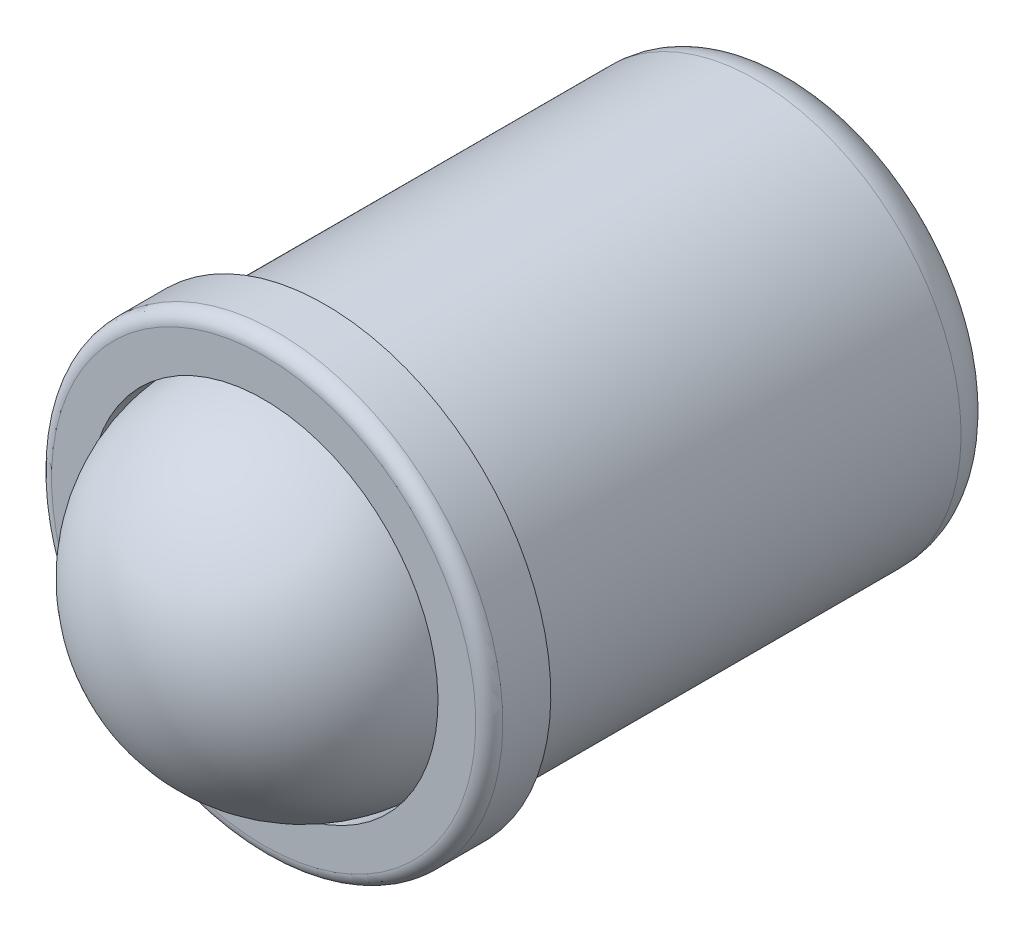
SolidWorks part; units mm, degrees
ref_plane "Front Plane" through (0, 0, 0) normal (0, 0, 1) x (1, 0, 0)
ref_plane "Top Plane" through (0, 0, 0) normal (0, 1, 0) x (1, 0, 0)
ref_plane "Right Plane" through (0, 0, 0) normal (1, 0, 0) x (0, 0, -1)
sketch "Sketch1" plane through (0, 0, 0) normal (1, 0, 0) x (0, 0, -1)
  line L0 (-8.15, 0) -> (8.15, 0) construction
  line L2 (8.15, 2.5) -> (8.15, 5)
  line L3 (8.15, 5) -> (-3.35, 5)
  line L4 (-3.35, 5) -> (-3.35, 5.5)
  line L5 (-3.35, 5.5) -> (-4.85, 5.5)
  line L6 (-4.85, 5.5) -> (-4.85, 4.25)
  line L8 (7.4, 4.25) -> (7.4, 2.5)
  line L9 (7.4, 2.5) -> (8.15, 2.5)
  line L10 (-4.85, 4.25) -> (7.4, 4.25)
  line L11 (-3.9, 0) -> (-3.9, 4.25) construction
  line L12 (-3.9, 4.25) -> (6.9625, 4.25) construction
  line L13 (6.9625, 4.25) -> (6.9625, 3.375) construction
  line L14 (6.9625, 3.375) -> (6.9625, 2.5) construction
  line L15 (6.9625, 2.5) -> (7.4, 2.5) construction
  circle A0 centre (-3.9, 0) radius 4.25
  arc A1 (7.4, 3.75) -> (6.9, 4.25) centre (6.9, 3.75) ccw
  arc A2 (8.15, 4) -> (7.15, 5) centre (7.15, 4) ccw
  arc A3 (-4.52, 5.5) -> (-4.85, 5.17) centre (-4.52, 5.17) ccw
  circle A4 centre (6.9625, 3.375) radius 0.4375
  point P27 (6.9625, 3.8125)
  dimension "R1" = 0.33
  dimension "R2" = 0.5
  dimension "R3" = 1
  dimension "Flange Thickness" = 1.5
  dimension "Body Diameter" = 10
  dimension "Extended Nose Length" = 3.3
  dimension "Rear Inner Diameter" = 5
  dimension "Wall Thickness" = 0.75
  dimension "Flange Diameter" = 11
  dimension "Body Length" = 11.5
  dimension "Nose Diameter" = 8.5
sketch "Sketch2" plane through (0, 0, 0) normal (1, 0, 0) x (0, 0, -1)
  line L0 (7.4, 2.5) -> (8.15, 2.5) construction
  line L2 (8.15, 2.5) -> (8.15, 5) construction
  line L3 (8.15, 5) -> (-3.35, 5) construction
  line L4 (-3.35, 5) -> (-3.35, 5.5) construction
  line L5 (7.4, 4.25) -> (7.4, 2.5) construction
  line L6 (7.4, 3.75) -> (7.4, 2.5)
  line L8 (-4.85, 5.5) -> (-4.85, 4.25) construction
  line L9 (-3.35, 5.5) -> (-4.85, 5.5) construction
  line L10 (7.4, 2.5) -> (8.15, 2.5)
  line L12 (8.15, 2.5) -> (8.15, 4)
  line L13 (7.15, 5) -> (-3.35, 5)
  line L14 (-3.35, 5) -> (-3.35, 5.5)
  line L18 (-4.85, 5.17) -> (-4.85, 4.25)
  line L19 (-3.35, 5.5) -> (-4.52, 5.5)
  line L20 (-4.85, 4.25) -> (7.4, 4.25) construction
  line L21 (-4.85, 4.25) -> (6.9, 4.25)
  arc A0 (7.4, 3.75) -> (6.9, 4.25) centre (6.9, 3.75) ccw construction
  arc A1 (8.15, 4) -> (7.15, 5) centre (7.15, 4) ccw construction
  arc A2 (-4.52, 5.5) -> (-4.85, 5.17) centre (-4.52, 5.17) ccw construction
  arc A3 (7.4, 3.75) -> (6.9, 4.25) centre (6.9, 3.75) ccw
  arc A4 (8.15, 4) -> (7.15, 5) centre (7.15, 4) ccw
  arc A5 (-4.52, 5.5) -> (-4.85, 5.17) centre (-4.52, 5.17) ccw
revolve "Revolve1" add sketch "Sketch2" angle 360 about L0
sketch "Sketch3" plane through (0, 0, 0) normal (1, 0, 0) x (0, 0, -1)
  line L0 (-8.15, 0) -> (8.15, 0) construction
  line L1 (-8.15, 0) -> (0.35, 0)
  circle A0 centre (-3.9, 0) radius 4.25 construction
  arc A1 (0.35, 0) -> (-8.15, 0) centre (-3.9, 0) ccw
revolve "Revolve2" add sketch "Sketch3" angle 360 about L1
ref_plane "Plane1" through (0, 0, -6.9625) normal (0, 0, 1) x (1, 0, 0)
sketch "Sketch4" plane through (0, 0, -6.9625) normal (0, 0, 1) x (1, 0, 0)
  circle A0 centre (0, 0) radius 3.375
curve "Helix/Spiral1" pitch 2.625 height 7.05 radius 3.375 centre (0, 0, -6.9625) axis (0, 0, 1) start towards (0, 1, 0)
sketch "Sketch5" plane through (0, 0, 0) normal (1, 0, 0) x (0, 0, -1)
  circle A0 centre (6.9625, 3.375) radius 0.4375 construction
  circle A1 centre (6.9625, 3.375) radius 0.4375
sweep "Sweep1" add profiles "Sketch5" path "Helix/Spiral1"
revolve "Revolve3" add sketch "Sketch5<2>" angle 360 about L0
sketch "Sketch5<2>" plane through (0, 0, 0) normal (1, 0, 0) x (0, 0, -1) same geometry as "Sketch5"
sketch "Sketch6" plane through (0, 0, 0) normal (0.3931, 0.9195, 0) x (0.9195, -0.3931, 0)
  circle A1 centre (3.375, -0.0883) radius 0.4375
  circle A2 centre (3.375, -0.0883) radius 0.4375
  dimension "D1" = 0
revolve "Revolve4" add sketch "Sketch6" angle 360 about L0
ref_plane "Contact Plane 1" through (0, 0, 8.15) normal (0, 0, 1) x (1, 0, 0)
equation "\"D3@Helix/Spiral1\"=(\"Body Length@Sketch1\"+\"Flange Thickness@Sketch1\"+\"Extended Nose Length@Sketch1\")-\"Nose Diameter@Sketch1\"-\"Wall Thickness@Sketch1\""
equation "\"D4@Helix/Spiral1\"=(\"Nose Diameter@Sketch1\"-\"Rear Inner Diameter@Sketch1\")*.75"
equation "\"R2@Sketch1\"=.5*\"R3@Sketch1\""
